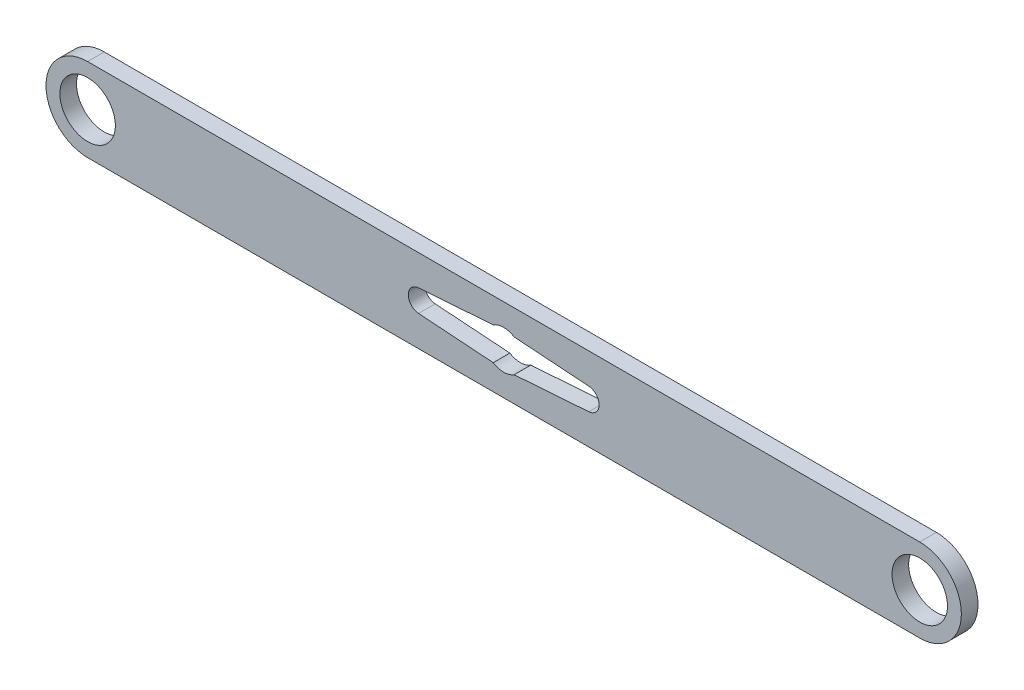
SolidWorks part; units mm, degrees
material "Acrylic (Medium-high impact)"
ref_plane "Front Plane" through (0, 0, 0) normal (0, 0, 1) x (1, 0, 0)
ref_plane "Top Plane" through (0, 0, 0) normal (0, 1, 0) x (1, 0, 0)
ref_plane "Right Plane" through (0, 0, 0) normal (1, 0, 0) x (0, 0, -1)
sketch "Sketch1" plane through (0, 0, 0) normal (0, 0, 1) x (1, 0, 0)
  line L0 (75, 0) -> (-75, 0) construction
  line L1 (75, -7.5) -> (-75, -7.5)
  line L2 (75, 7.5) -> (-75, 7.5)
  line L3 (-1.8835, 2.95) -> (-15.3416, 1.995)
  line L5 (0, 3.5) -> (0, -3.5) construction
  line L11 (-1.8835, -2.95) -> (-15.3416, -1.995)
  line L12 (1.8835, -2.95) -> (15.3416, -1.995)
  line L13 (1.8835, 2.95) -> (15.3416, 1.995)
  arc A0 (75, -7.5) -> (75, 7.5) centre (75, 0) ccw
  arc A1 (-75, 7.5) -> (-75, -7.5) centre (-75, 0) ccw
  circle A2 centre (75, 0) radius 5
  circle A3 centre (-75, 0) radius 5
  arc A16 (-1.8835, -2.95) -> (1.8835, -2.95) centre (0, 0) ccw
  arc A17 (-15.3416, 1.995) -> (-15.3416, -1.995) centre (-15.2, 0) ccw
  arc A18 (15.3416, 1.995) -> (15.3416, -1.995) centre (15.2, 0) cw
  arc A19 (-1.8835, 2.95) -> (-3.5, 0) centre (0, 0) ccw construction
  arc A20 (-3.5, 0) -> (-1.8835, -2.95) centre (0, 0) ccw construction
  arc A21 (1.8835, -2.95) -> (3.5, 0) centre (0, 0) ccw construction
  arc A22 (1.8835, 2.95) -> (-1.8835, 2.95) centre (0, 0) ccw
  arc A23 (3.5, 0) -> (1.8835, 2.95) centre (0, 0) ccw construction
  point P2 (0, 0)
  point P25 (-17.2, 0)
  dimension "D2" = 10
  dimension "D8" = 2
  dimension "D4" = 10
  dimension "D6" = 5.9
  dimension "D7" = 17.2
  dimension "D5" = 7
  dimension "D1" = 150
  dimension "D3" = 15
extrude "Boss-Extrude1" add sketch "Sketch1" along normal blind 3
